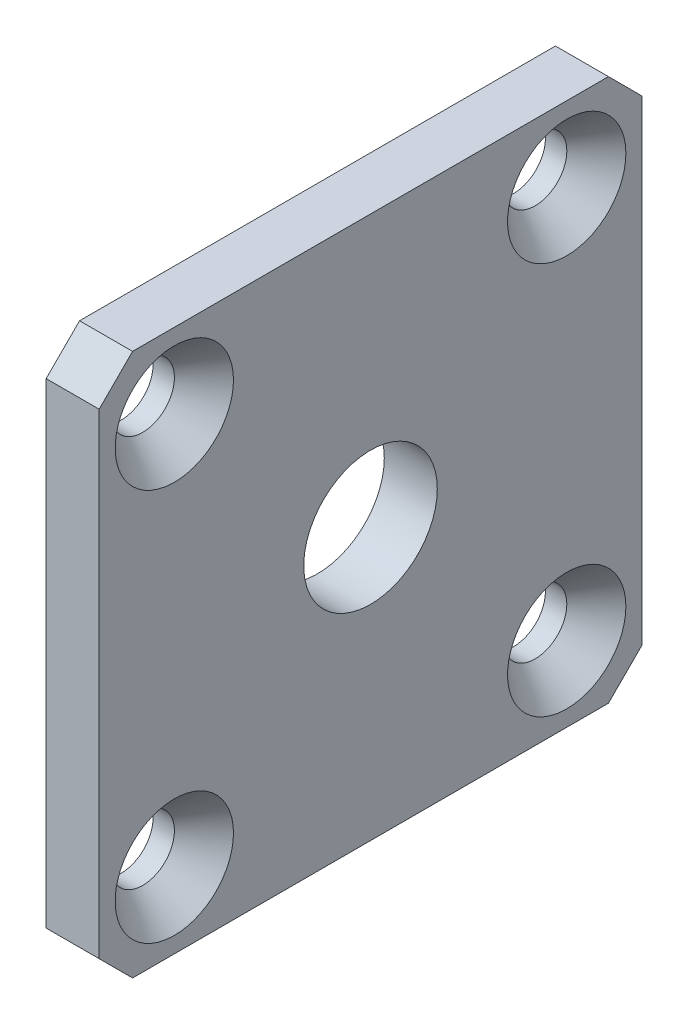
SolidWorks part; units mm, degrees
material "6061-T6 (SS)"
ref_plane "Front" through (0, 0, 0) normal (0, 0, 1) x (1, 0, 0)
ref_plane "Top" through (0, 0, 0) normal (0, 1, 0) x (1, 0, 0)
ref_plane "Right" through (0, 0, 0) normal (1, 0, 0) x (0, 0, -1)
ref_axis "side-side" through (80.9, 0, 0) along (-1, 0, 0)
ref_axis "up-down" through (0, 50, 0) along (0, -1, 0)
ref_axis "front-back" through (0, 0, -80.9) along (0, 0, 1)
sketch "Sketch1" plane through (0, 0, 0) normal (1, 0, 0) x (0, 0, -1)
  line L0 (-16.25, 16.25) -> (16.25, -16.25) construction
  line L1 (-16.25, 16.25) -> (16.25, 16.25)
  line L2 (-16.25, 16.25) -> (-16.25, -16.25)
  line L3 (-16.25, -16.25) -> (16.25, -16.25)
  line L4 (16.25, 16.25) -> (16.25, -16.25)
  circle A0 centre (0, 0) radius 4
  circle A1 centre (-11.75, 11.75) radius 3.55 construction
  circle A2 centre (0, 0) radius 16.617 construction
  circle A3 centre (11.75, 11.75) radius 3.55 construction
  circle A4 centre (-11.75, -11.75) radius 3.55 construction
  circle A5 centre (11.75, -11.75) radius 3.55 construction
  circle A6 centre (0, 0) radius 15 construction
  dimension "D1" = 8
  dimension "D4" = 7.1
  dimension "D5" = 12.617
  dimension "D6" = 30
  dimension "D2" = 32.5
  dimension "D3" = 4.5
extrude "Boss-Extrude1" add sketch "Sketch1" along normal blind 3.175
chamfer "Chamfer1" distance 2 angle 45 4 edges at (1.5875, -16.25, -16.25) (1.5875, -16.25, 16.25) (1.5875, 16.25, -16.25) (1.5875, 16.25, 16.25)
hole_wizard "CSK for #6 Flat Head Machine Screw1" positions "Sketch2" profile "Sketch3" countersink size "#6" standard "ANSI Inch" end condition through all
sketch "Sketch2" plane through (3.175, 0, 0) normal (1, 0, 0) x (0, 0, -1)
  point P0 (-11.75, 11.75)
  point P4 (11.75, 11.75)
  point P7 (11.75, -11.75)
  point P10 (-11.75, -11.75)
sketch "Sketch3" plane through (3.175, 11.75, 11.75) normal (0, 1, 0) x (0, 0, -1)
  line L0 (0, 0) -> (0, 3.175)
  line L1 (0, 3.175) -> (1.8986, 3.175)
  line L2 (1.8986, 3.175) -> (1.8986, 1.892)
  line L3 (1.8986, 1.892) -> (3.5433, 0)
  line L5 (3.5433, 0) -> (0, 0)
  line L6 (-1.8986, 1.892) -> (-3.5433, 0) construction
  line L11 (0, -6.35) -> (0, 107.95) construction
  dimension "Thru Hole Dia." = 3.7973
  dimension "Thru Hole Depth" = 3.175
  dimension "Near C'Sink Dia." = 7.0866
  dimension "Near C'Sink Angle" = 82
